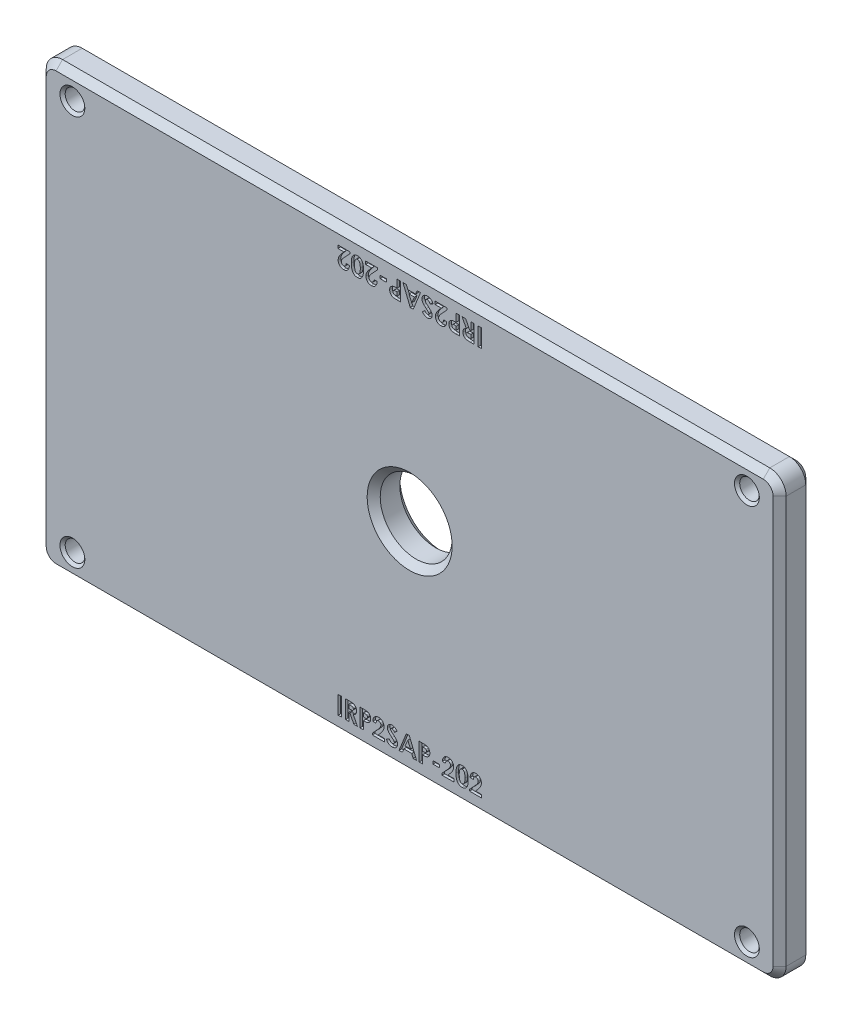
SolidWorks part; units mm, degrees
material "6061-T6 (SS)"
ref_plane "Front" through (0, 0, 0) normal (0, 0, 1) x (1, 0, 0)
ref_plane "Top" through (0, 0, 0) normal (0, 1, 0) x (1, 0, 0)
ref_plane "Right" through (0, 0, 0) normal (1, 0, 0) x (0, 0, -1)
sketch "Sketch1" plane through (0, 0, 0) normal (0, 0, 1) x (1, 0, 0)
  line L0 (-65.4844, 37.9412) -> (65.4844, 37.9412) construction
  line L1 (-71.8344, -42.7037) -> (71.8344, -42.7037)
  line L2 (-71.8344, -42.7037) -> (-71.8344, 42.7037)
  line L3 (-71.8344, 42.7037) -> (71.8344, 42.7037)
  line L4 (71.8344, -42.7037) -> (71.8344, 42.7037)
  line L5 (-71.8344, -42.7037) -> (71.8344, 42.7037) construction
  line L6 (-71.8344, 42.7037) -> (71.8344, -42.7037) construction
  line L7 (65.4844, 37.9412) -> (65.4844, -37.9412) construction
  line L8 (65.4844, -37.9412) -> (-65.4844, -37.9412) construction
  line L9 (-65.4844, -37.9412) -> (-65.4844, 37.9412) construction
  line L10 (-71.8344, 0) -> (-65.4844, 0) construction
  line L11 (-65.4844, 0) -> (0, 37.9412) construction
  line L12 (0, 37.9412) -> (0, 42.7037) construction
  circle A0 centre (0, 0) radius 6.985
  circle A1 centre (-65.4844, 37.9412) radius 1.905
  circle A2 centre (65.4844, 37.9412) radius 1.905
  circle A3 centre (65.4844, -37.9412) radius 1.905
  circle A4 centre (-65.4844, -37.9412) radius 1.905
  point P0 (0, 0)
  dimension "D1" = 13.97
  dimension "D2" = 3.81
  dimension "D3" = 4.7625
  dimension "D4" = 6.35
  dimension "D5" = 143.6687
  dimension "D6" = 85.4075
extrude "Boss-Extrude1" add sketch "Sketch1" against normal blind 6.35
fillet "Fillet1" radius 3.175 4 edges at (71.8344, -42.7037, -3.175) (71.8344, 42.7037, -3.175) (-71.8344, -42.7037, -3.175) (-71.8344, 42.7037, -3.175)
chamfer "Chamfer1" distance 1.27 angle 45 18 edges at (6.985, 0, 0) (6.985, 0, -6.35) (0, -42.7037, -6.35) (70.9044, -41.7738, -6.35) (-70.9044, -41.7738, -6.35) (71.8344, 0, -6.35) (-71.8344, 0, -6.35) (70.9044, 41.7738, -6.35) (-70.9044, 41.7738, -6.35) (0, 42.7037, -6.35) (0, -42.7037, 0) (70.9044, -41.7738, 0) (-70.9044, -41.7738, 0) (71.8344, 0, 0) (-71.8344, 0, 0) (70.9044, 41.7738, 0) (-70.9044, 41.7738, 0) (0, 42.7037, 0)
chamfer "Chamfer2" distance 0.508 angle 45 8 edges at (67.3894, -37.9412, 0) (67.3894, -37.9412, -6.35) (67.3894, 37.9412, 0) (67.3894, 37.9412, -6.35) (-63.5794, 37.9412, 0) (-63.5794, 37.9412, -6.35) (-63.5794, -37.9412, 0) (-63.5794, -37.9412, -6.35)
sketch "Sketch2" plane through (0, 0, 0) normal (0, 0, 1) x (1, 0, 0)
  line L0 (-70.5644, -39.5288) -> (70.5644, -39.5288) construction
  line L1 (-70.5644, 39.5288) -> (-70.5644, -39.5288) construction
  line L2 (70.5644, -39.5288) -> (70.5644, 39.5288) construction
  line L3 (-68.6594, 42.7037) -> (68.6594, 42.7037) construction
  line L4 (-70.5644, 39.5288) -> (70.5644, 39.5288) construction
  line L5 (68.6594, -42.7037) -> (-68.6594, -42.7037) construction
  text T0 "<b>IRP2SAP-202</b>"
  text T1 "<b>IRP2SAP-202</b>"
  dimension "D1" = 3.175
  dimension "D2" = 3.175
extrude "Cut-Extrude1" cut sketch "Sketch2" against normal blind 0.508
sketch "Sketch3" plane through (0, 0, -6.35) normal (0, 0, -1) x (-1, 0, 0)
  line L0 (-70.5644, 39.5287) -> (70.5644, 39.5288) construction
  line L1 (-70.5644, 39.5288) -> (-70.5644, -39.5288) construction
  line L2 (70.5644, -39.5288) -> (70.5644, 39.5288) construction
  line L3 (-68.6594, 42.7037) -> (68.6594, 42.7037) construction
  line L4 (-70.5644, -39.5288) -> (70.5644, -39.5288) construction
  line L5 (68.6594, -42.7037) -> (-68.6594, -42.7037) construction
  text T0 "<b>IRP2SAP-202</b>"
  text T1 "<b>IRP2SAP-202</b>"
  dimension "D1" = 3.175
  dimension "D2" = 3.175
extrude "Cut-Extrude2" cut sketch "Sketch3" against normal blind 0.508
